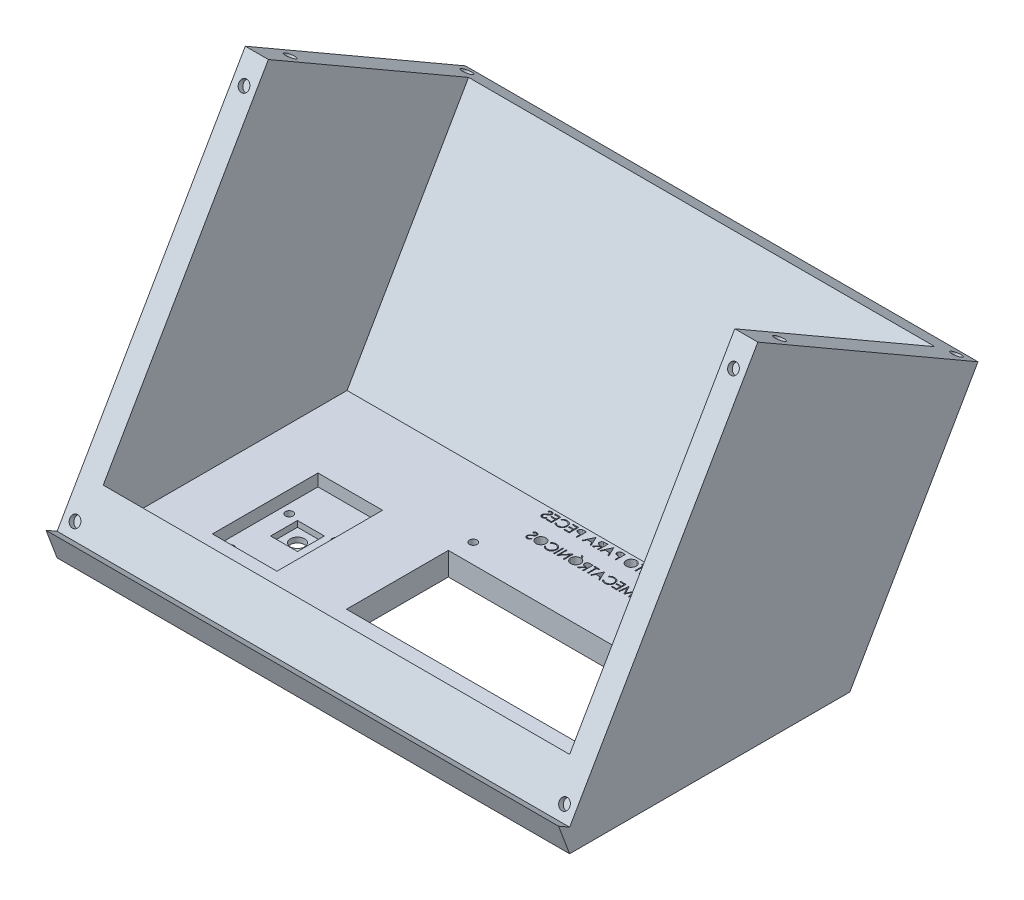
SolidWorks part; units mm, degrees
ref_plane "Front Plane" through (0, 0, 0) normal (0, 0, 1) x (1, 0, 0)
ref_plane "Top Plane" through (0, 0, 0) normal (0, 1, 0) x (1, 0, 0)
ref_plane "Right Plane" through (0, 0, 0) normal (1, 0, 0) x (0, 0, -1)
sketch "Croquis1" plane through (0, 0, 0) normal (0, 1, 0) x (1, 0, 0)
  line L1 (-100, -50) -> (100, -50)
  line L2 (-100, -50) -> (-100, 50)
  line L3 (-100, 50) -> (100, 50)
  line L4 (100, -50) -> (100, 50)
  line L5 (-100, -50) -> (100, 50) construction
  line L6 (-100, 50) -> (100, -50) construction
  point P0 (0, 0)
  dimension "D1" = 200
  dimension "D2" = 100
extrude "Saliente-Extruir1" add sketch "Croquis1" along normal blind 9
sketch "Croquis20" plane through (-100, 0, 0) normal (-1, 0, 0) x (0, 0, 1)
  line L0 (50, 9) -> (-23.4406, 136.2028)
  line L2 (-109.3509, 86.6025) -> (-23.4406, 136.2028)
  line L3 (-109.3509, 86.6025) -> (-59.3509, 0)
  line L4 (-59.3509, 0) -> (-50, 0)
  line L9 (-50, 0) -> (50, 0)
  line L10 (50, 0) -> (50, 9)
  line L11 (50, 9) -> (-50, 9)
  line L12 (-50, 9) -> (-50, 0)
  line L15 (50, 9) -> (-50, 9)
  line L16 (-50, 9) -> (-50, 0)
  dimension "D1" = 0
  dimension "D7" = 100
extrude "Saliente-Extruir2" add sketch "Croquis20" against normal up to surface (200 mm away) up to face at (100, 4.5, 0)
shell "Vaciado4" thickness 9
sketch "Croquis11" plane through (20.3343, 0, -104.1539) normal (0, -1, 0) x (-1, 0, 0)
  line L0 (20.3343, -54.1539) -> (20.3343, -154.1539) construction
  line L1 (-79.6657, -154.1539) -> (120.3343, -154.1539) construction
  line L2 (-79.6657, -154.1539) -> (-79.6657, -54.1539) construction
  line L3 (-79.6657, -54.1539) -> (120.3343, -54.1539) construction
  line L4 (120.3343, -154.1539) -> (120.3343, -54.1539) construction
  line L5 (-79.6657, -154.1539) -> (-79.6657, -44.803) construction
  line L11 (-59.6657, -124.0305) -> (37.5343, -124.0305)
  line L13 (-79.6657, -154.1539) -> (-79.6657, -44.803) construction
  line L14 (120.3343, -154.1539) -> (-79.6657, -154.1539) construction
  line L15 (-79.6657, -44.803) -> (120.3343, -44.803) construction
  line L17 (-59.6657, -84.2772) -> (37.5343, -84.2772)
  line L18 (-59.6657, -84.2772) -> (-59.6657, -124.0305)
  line L20 (37.5343, -84.2772) -> (37.5343, -124.0305)
  circle A0 centre (76.5343, -104.1539) radius 2.75
  point P6 (-21.0657, -104.1539)
  dimension "D5" = 5.5
  dimension "D1" = 20
  dimension "D2" = 58.6
  dimension "D3" = 117.2
  dimension "D4" = 156.2
  dimension "D6" = 30.1233
  dimension "D7" = 50
  dimension "D8" = 9.3509
  dimension "D9" = 69.8767
extrude "Cortar-Extruir5" cut sketch "Croquis11" against normal up to next
sketch "Croquis22" plane through (0, 9, 0) normal (0, 1, 0) x (1, 0, 0)
  line L1 (-68.8, -20.6) -> (-43.6, -20.6)
  line L2 (-68.8, -20.6) -> (-68.8, 20.6)
  line L3 (-68.8, 20.6) -> (-43.6, 20.6)
  line L4 (-43.6, -20.6) -> (-43.6, 20.6)
  line L5 (-68.8, -20.6) -> (-43.6, 20.6) construction
  line L6 (-68.8, 20.6) -> (-43.6, -20.6) construction
  point P0 (-56.2, 0)
  dimension "D1" = 25.2
  dimension "D2" = 41.2
extrude "Cortar-Extruir13" cut sketch "Croquis22" against normal blind 4.7
sketch "Croquis23" plane through (0, 9, 0) normal (0, 1, 0) x (1, 0, 0)
  line L1 (-61.45, 5.25) -> (-50.95, 5.25)
  line L2 (-61.45, 5.25) -> (-61.45, -5.25)
  line L3 (-61.45, -5.25) -> (-50.95, -5.25)
  line L4 (-50.95, 5.25) -> (-50.95, -5.25)
  line L5 (-61.45, 5.25) -> (-50.95, -5.25) construction
  line L6 (-61.45, -5.25) -> (-50.95, 5.25) construction
  point P0 (-56.2, 0)
  dimension "D1" = 10.5
  dimension "D2" = 10.5
extrude "Cortar-Extruir14" cut sketch "Croquis23" against normal blind 7
sketch "Croquis24" plane through (0, 112.3022, -64.8377) normal (0, 0.866, -0.5) x (1, 0, 0)
  line L0 (-100, -47.8013) -> (-100, 51.3993) construction
  line L1 (-91, -47.8013) -> (-100, -47.8013) construction
  line L2 (0, -74.9116) -> (0, 74.9116) construction
  line L3 (91, 42.3993) -> (-91, 42.3993) construction
  circle A0 centre (-95.5, -32.8013) radius 2.05
  circle A1 centre (95.5, -32.8013) radius 2.05
  circle A2 centre (-95.5, 46.8993) radius 2.05
  circle A4 centre (95.5, 46.8993) radius 2.05
  point P16 (0, 0)
  dimension "D1" = 4.1
  dimension "D6" = 4.1
  dimension "D2" = 4.5
  dimension "D3" = 15
  dimension "D4" = 4.5
  dimension "D5" = 4.5
extrude "Cortar-Extruir15" cut sketch "Croquis24" against normal blind 2.1
sketch "Croquis25" plane through (0, 23.9006, 41.3971) normal (0, 0.5, 0.866) x (1, 0, 0)
  line L0 (-91, 129.6754) -> (-100, 129.6754) construction
  line L1 (-100, -17.2058) -> (-100, 129.6754) construction
  line L2 (-100, -17.2058) -> (100, -17.2058) construction
  line L3 (0, -74.9116) -> (0, 74.9116) construction
  circle A0 centre (-95.5, 119.6754) radius 2.05
  circle A1 centre (-95.5, -12.2058) radius 2.05
  circle A2 centre (95.5, -12.2058) radius 2.05
  circle A3 centre (95.5, 119.6754) radius 2.05
  dimension "D1" = 4.1
  dimension "D6" = 4.1
  dimension "D2" = 10
  dimension "D3" = 4.5
  dimension "D4" = 5
  dimension "D5" = 4.5
extrude "Cortar-Extruir16" cut sketch "Croquis25" against normal blind 2.1
sketch "Croquis26" plane through (0, 0, 0) normal (0, -1, 0) x (1, 0, 0)
  line L0 (100, -49.3509) -> (-21.8644, -49.3509) construction
  line L1 (100, 50) -> (100, -59.3509) construction
  line L2 (100, -59.3509) -> (-100, -59.3509) construction
  line L3 (100, -39.3509) -> (-21.8644, -39.3509) construction
  text T0 "DOSIFICADOR DE ALIMENTO PARA PECES"
  text T1 "DISEÑO DE SISTEMAS MECATRÓNICOS\r\n"
  dimension "D1" = 10
  dimension "D2" = 10
extrude "Cortar-Extruir18" cut sketch "Croquis26" against normal up to surface (9 mm away)
sketch "Croquis28" plane through (0, 4.3, 0) normal (0, 1, 0) x (1, 0, 0)
  line L0 (-68.8, -20.6) -> (-43.6, -20.6) construction
  line L1 (-68.8, 20.6) -> (-68.8, -20.6) construction
  line L2 (-56.2, 20.6) -> (-56.2, -20.6) construction
  line L3 (-68.8, -20.6) -> (-43.6, -20.6) construction
  line L4 (-68.8, 0) -> (-43.6, 0) construction
  line L5 (-43.6, -20.6) -> (-43.6, 20.6) construction
  circle A0 centre (-65.3, -17.1) radius 1.5
  circle A1 centre (-47.1, -17.1) radius 1.5
  circle A2 centre (-65.3, 5.9) radius 1.5
  circle A3 centre (-47.1, 5.9) radius 1.5
  point P2 (-65.3, -18.6)
  point P3 (-66.8, -17.1)
  point P14 (-56.2, 0)
  point P19 (-56.2, 0)
  point P23 (-65.3, 4.4)
  point P24 (-66.8, 5.9)
  dimension "D1" = 3
  dimension "D4" = 3
  dimension "D2" = 2
  dimension "D3" = 2
  dimension "D5" = 25
  dimension "D6" = 2
extrude "Cortar-Extruir19" cut sketch "Croquis28" against normal blind 3
sketch "Croquis29" plane through (0, 9, 0) normal (0, 1, 0) x (1, 0, 0)
  line L0 (-17.2, 19.8767) -> (80, -19.8767) construction
  line L1 (-17.2, -19.8767) -> (80, 19.8767) construction
  line L2 (31.4, 30) -> (31.4, -30) construction
  line L3 (80.4, -30) -> (-17.6, -30) construction
  line L4 (80.4, -30) -> (80.4, 30) construction
  line L5 (80.4, 30) -> (-17.6, 30) construction
  line L6 (-17.6, -30) -> (-17.6, 30) construction
  line L7 (80.4, -30) -> (-17.6, 30) construction
  line L8 (80.4, 30) -> (-17.6, -30) construction
  circle A0 centre (-15.1, 27.5) radius 1.5
  circle A1 centre (-15.6, -27.5) radius 1.5
  circle A2 centre (78.4, -27.5) radius 1.5
  circle A3 centre (77.9, 27.5) radius 1.5
  point P8 (31.4, 0)
  point P9 (31.4, 0)
  point P16 (-16.6, 27.5)
  point P17 (-15.1, 29)
  point P21 (31.4, 0)
  point P24 (31.4, 0)
  point P26 (-15.6, -29)
  point P27 (-17.1, -27.5)
  dimension "D3" = 3
  dimension "D6" = 3
  dimension "D1" = 60
  dimension "D2" = 98
  dimension "D4" = 1
  dimension "D5" = 1
  dimension "D7" = 1
  dimension "D8" = 1
extrude "Cortar-Extruir20" cut sketch "Croquis29" against normal blind 3
sketch "Croquis30" plane through (-100, 0, 0) normal (-1, 0, 0) x (0, 0, 1)
  line L0 (50, 9) -> (54.3301, 11.5)
  line L1 (54.3301, 11.5) -> (50, 0)
  line L2 (50, 0) -> (50, 9)
  line L3 (50, 9) -> (50, 0) construction
  line L6 (50, 9) -> (-23.4406, 136.2028) construction
  point P3 (49.8263, 9.3008)
  dimension "D1" = 5
extrude "Saliente-Extruir3" add sketch "Croquis30" against normal through all
